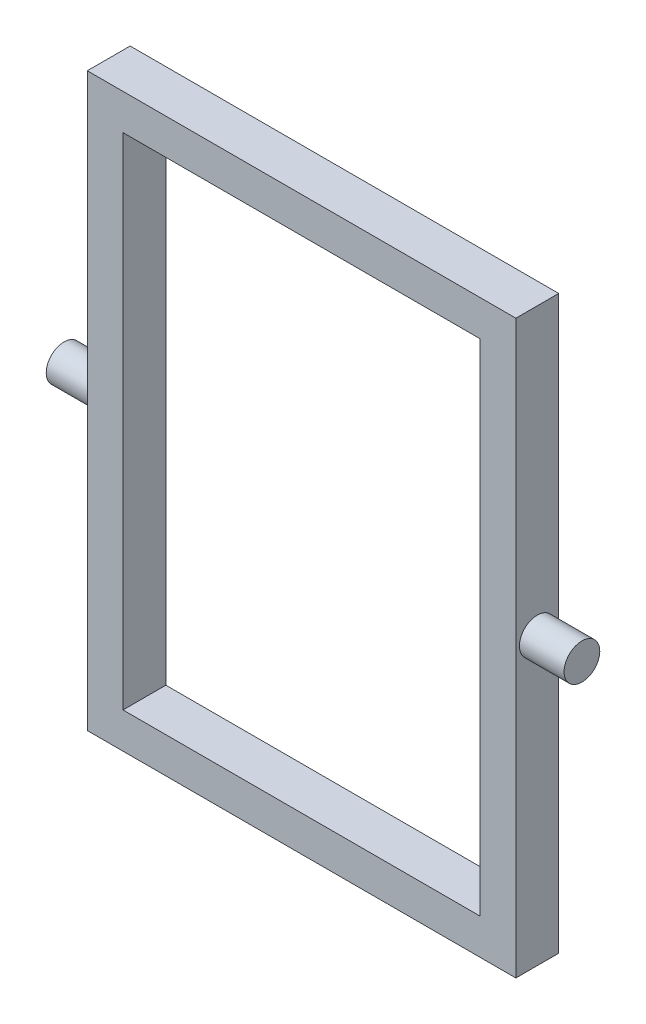
SolidWorks part; units mm, degrees
ref_plane "Front Plane" through (0, 0, 0) normal (0, 0, 1) x (1, 0, 0)
ref_plane "Top Plane" through (0, 0, 0) normal (0, 1, 0) x (1, 0, 0)
ref_plane "Right Plane" through (0, 0, 0) normal (1, 0, 0) x (0, 0, -1)
sketch "Sketch2" plane through (0, 0, 0) normal (0, 0, 1) x (1, 0, 0)
  line L1 (-250, 350) -> (250, 350)
  line L2 (-250, 350) -> (-250, -350)
  line L3 (-250, -350) -> (250, -350)
  line L4 (250, 350) -> (250, -350)
  line L5 (-250, 350) -> (250, -350) construction
  line L6 (-250, -350) -> (250, 350) construction
  line L7 (-300, 400) -> (300, 400)
  line L8 (-300, 400) -> (-300, -400)
  line L9 (-300, -400) -> (300, -400)
  line L10 (300, 400) -> (300, -400)
  line L11 (-300, 400) -> (300, -400) construction
  line L12 (-300, -400) -> (300, 400) construction
  point P0 (0, 0)
  point P6 (0, 0)
  dimension "D1" = 700
  dimension "D2" = 500
  dimension "D3" = 800
  dimension "D4" = 600
extrude "Boss-Extrude1" add sketch "Sketch2" along normal blind 30 and the other way blind 30
sketch "Sketch3" plane through (300, 0, 0) normal (1, 0, 0) x (0, 0, -1)
  circle A0 centre (0, 0) radius 25
  dimension "D1" = 50
extrude "Boss-Extrude2" add sketch "Sketch3" along normal blind 62.5
mirror "Mirror1" about plane through (0, 0, 0) normal (1, 0, 0) of "Boss-Extrude2"
